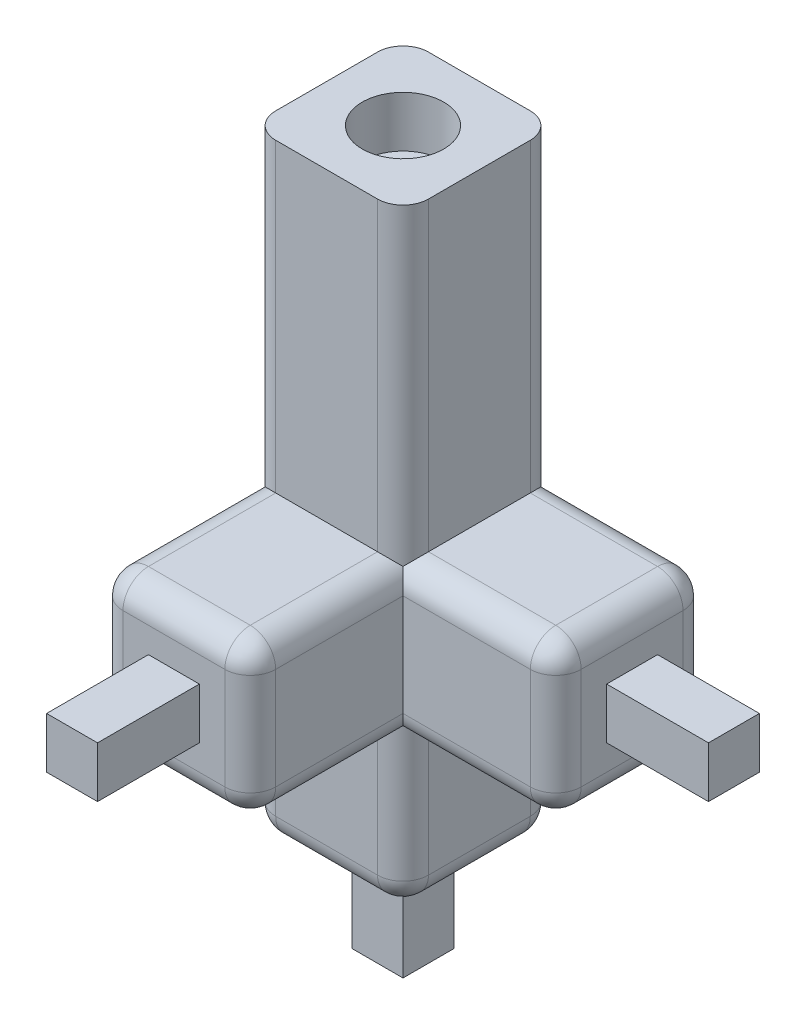
SolidWorks part; units mm, degrees
ref_plane "Front Plane" through (0, 0, 0) normal (0, 0, 1) x (1, 0, 0)
ref_plane "Top Plane" through (0, 0, 0) normal (0, 1, 0) x (1, 0, 0)
ref_plane "Right Plane" through (0, 0, 0) normal (1, 0, 0) x (0, 0, -1)
sketch "Sketch1" plane through (0, 0, 0) normal (0, 1, 0) x (1, 0, 0)
  line L1 (-7.5, 7.5) -> (7.5, 7.5)
  line L2 (-7.5, 7.5) -> (-7.5, -7.5)
  line L3 (-7.5, -7.5) -> (7.5, -7.5)
  line L4 (7.5, 7.5) -> (7.5, -7.5)
  line L5 (-7.5, 7.5) -> (7.5, -7.5) construction
  line L6 (-7.5, -7.5) -> (7.5, 7.5) construction
  point P0 (0, 0)
  dimension "D1" = 15
  dimension "D2" = 15
extrude "Boss-Extrude1" add sketch "Sketch1" along normal blind 45
sketch "Sketch2" plane through (0, 0, 7.5) normal (0, 0, 1) x (1, 0, 0)
  line L0 (-7.5, 22.5) -> (7.5, 22.5) construction
  line L1 (-7.5, 45) -> (-7.5, 0) construction
  line L2 (7.5, 45) -> (7.5, 0) construction
  line L4 (-7.5, 30) -> (7.5, 30)
  line L5 (-7.5, 30) -> (-7.5, 15)
  line L6 (-7.5, 15) -> (7.5, 15)
  line L7 (7.5, 30) -> (7.5, 15)
  line L8 (-7.5, 30) -> (7.5, 15) construction
  line L9 (-7.5, 15) -> (7.5, 30) construction
  point P6 (0, 22.5)
  dimension "D1" = 15
  dimension "D2" = 15
extrude "Boss-Extrude2" add sketch "Sketch2" along normal blind 15
sketch "Sketch5" plane through (7.5, 0, 0) normal (1, 0, 0) x (0, 0, -1)
  line L0 (0, 45) -> (0, 0) construction
  line L1 (-7.5, 45) -> (7.5, 45) construction
  line L3 (7.5, 30) -> (-7.5, 30)
  line L4 (7.5, 30) -> (7.5, 15)
  line L5 (7.5, 15) -> (-7.5, 15)
  line L6 (-7.5, 30) -> (-7.5, 15)
  line L7 (7.5, 30) -> (-7.5, 15) construction
  line L8 (7.5, 15) -> (-7.5, 30) construction
  point P5 (0, 22.5)
extrude "Boss-Extrude5" add sketch "Sketch5" along normal blind 15
sketch "Sketch6" plane through (0, 45, 0) normal (0, 1, 0) x (1, 0, 0)
  line L1 (-7.5, 7.5) -> (7.5, 7.5)
  line L2 (-7.5, 7.5) -> (-7.5, -7.5)
  line L3 (-7.5, -7.5) -> (7.5, -7.5)
  line L4 (7.5, 7.5) -> (7.5, -7.5)
  line L5 (-7.5, 7.5) -> (7.5, -7.5) construction
  line L6 (-7.5, -7.5) -> (7.5, 7.5) construction
  point P0 (0, 0)
extrude "Boss-Extrude6" add sketch "Sketch6" along normal blind 15
fillet "Fillet2" radius 2.5 8 edges at (-7.5, 15, 15) (0, 15, 22.5) (-7.5, 22.5, 22.5) (7.5, 22.5, 22.5) (7.5, 15, 15) (7.5, 30, 15) (0, 30, 22.5) (-7.5, 30, 15)
fillet "Fillet3" radius 2.5 8 edges at (15, 15, -7.5) (22.5, 22.5, -7.5) (22.5, 15, 0) (15, 15, 7.5) (22.5, 22.5, 7.5) (15, 30, -7.5) (22.5, 30, 0) (15, 30, 7.5)
fillet "Fillet4" radius 2.5 9 edges at (0, 0, -7.5) (-7.5, 0, 0) (7.5, 8.75, -7.5) (7.5, 0, 0) (-7.5, 8.75, 7.5) (7.5, 8.75, 7.5) (0, 0, 7.5) (-7.5, 30, -7.5) (7.5, 43.75, -7.5)
sketch "Sketch7" plane through (0, 0, 22.5) normal (0, 0, 1) x (1, 0, 0)
  line L0 (0, 27.5) -> (0, 17.5) construction
  line L1 (5, 27.5) -> (-5, 27.5) construction
  line L2 (-5, 17.5) -> (5, 17.5) construction
  line L4 (-2.5, 25) -> (2.5, 25)
  line L5 (-2.5, 25) -> (-2.5, 20)
  line L6 (-2.5, 20) -> (2.5, 20)
  line L7 (2.5, 25) -> (2.5, 20)
  line L8 (-2.5, 25) -> (2.5, 20) construction
  line L9 (-2.5, 20) -> (2.5, 25) construction
  point P6 (0, 22.5)
  dimension "D1" = 5
  dimension "D2" = 5
extrude "Boss-Extrude7" add sketch "Sketch7" along normal blind 10
sketch "Sketch8" plane through (22.5, 0, 0) normal (1, 0, 0) x (0, 0, -1)
  line L0 (0, 27.5) -> (0, 17.5) construction
  line L1 (5, 27.5) -> (-5, 27.5) construction
  line L2 (-5, 17.5) -> (5, 17.5) construction
  line L4 (-2.5, 25) -> (2.5, 25)
  line L5 (-2.5, 25) -> (-2.5, 20)
  line L6 (-2.5, 20) -> (2.5, 20)
  line L7 (2.5, 25) -> (2.5, 20)
  line L8 (-2.5, 25) -> (2.5, 20) construction
  line L9 (-2.5, 20) -> (2.5, 25) construction
  point P6 (0, 22.5)
  dimension "D1" = 5
  dimension "D2" = 5
extrude "Boss-Extrude8" add sketch "Sketch8" along normal blind 10
sketch "Sketch9" plane through (0, 0, 0) normal (0, -1, 0) x (1, 0, 0)
  line L0 (0, 5) -> (0, -5) construction
  line L1 (5, 5) -> (-5, 5) construction
  line L2 (-5, -5) -> (5, -5) construction
  line L4 (-2.5, 2.5) -> (2.5, 2.5)
  line L5 (-2.5, 2.5) -> (-2.5, -2.5)
  line L6 (-2.5, -2.5) -> (2.5, -2.5)
  line L7 (2.5, 2.5) -> (2.5, -2.5)
  line L8 (-2.5, 2.5) -> (2.5, -2.5) construction
  line L9 (-2.5, -2.5) -> (2.5, 2.5) construction
  point P6 (0, 0)
  dimension "D1" = 5
  dimension "D2" = 5
extrude "Boss-Extrude9" add sketch "Sketch9" along normal blind 10
sketch "Sketch10" plane through (0, 60, 0) normal (0, 1, 0) x (1, 0, 0)
  line L0 (0, 7.5) -> (0, -7.5) construction
  line L1 (5, 7.5) -> (-5, 7.5) construction
  line L2 (-5, -7.5) -> (5, -7.5) construction
  circle A0 centre (0, 0) radius 4
  dimension "D1" = 8
extrude "Cut-Extrude1" cut sketch "Sketch10" against normal blind 5
